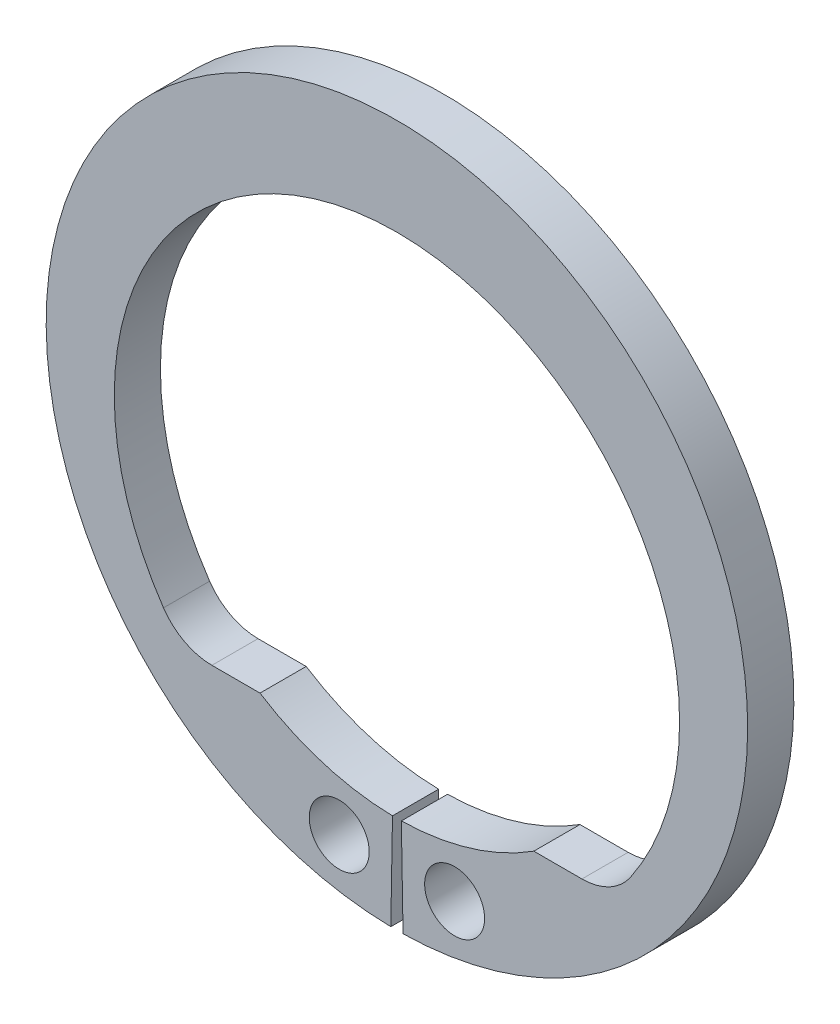
SolidWorks part; units mm, degrees
ref_plane "plane" through (0, 0, 0) normal (0, 0, 1) x (1, 0, 0)
ref_plane "Top" through (0, 0, 0) normal (0, 1, 0) x (1, 0, 0)
ref_plane "Right" through (0, 0, 0) normal (1, 0, 0) x (0, 0, -1)
sketch "Sketch 1" plane through (0, 0, 0) normal (0, 0, 1) x (1, 0, 0)
  line L0 (-5.75, 0) -> (5.75, 0) construction
  line L1 (0, 8.1) -> (0, -8.1) construction
  line L2 (-2.9663, -4.6315) -> (-4.6315, -4.6315) construction
  line L3 (-7.1976, 0) -> (7.1976, 0)
  line L4 (-4.6315, -4.6315) -> (-5.374, -5.374) construction
  line L5 (-4.6315, -4.6315) -> (0, 0) construction
  line L6 (0, 5.5) -> (0, 7.6) construction
  line L7 (0, 7.6) -> (0, 6.55) construction
  line L8 (0, -5.5) -> (0, -50.9099) construction
  line L9 (0, -5.5) -> (0, -6.55) construction
  line L10 (0, 0) -> (-0.1326, -7.5988) construction
  line L11 (0, -6.55) -> (0, -7.6) construction
  line L12 (0, 0) -> (-1.2498, -6.4297) construction
  line L13 (-7.1976, 0) -> (0, -26.6022) construction
  arc A0 (0, 7.6) -> (-4.6315, -4.6315) centre (0, 0.6073) ccw construction
  circle A1 centre (0, 0) radius 7.85 construction
  circle A2 centre (0, 0) radius 7.6 construction
  circle A4 centre (0, 0) radius 5.5 construction
  circle A5 centre (0, 0) radius 8.1 construction
  circle A6 centre (-1.2498, -6.4297) radius 0.65 construction
  arc A7 (-1.2498, -6.4297) -> (-0.1143, -6.549) centre (0, 0) ccw construction
  circle A8 centre (0, 0) radius 6.9478 construction
  point P22 (0, 0)
  point P28 (-7.1976, 0)
  point P32 (0, -26.6022)
  dimension "D1" = 1.4478
  dimension "Cad A" = 16.2
  dimension "D2" = 10
  dimension "Ring ID" = 11
  dimension "Cad C" = 15.7
  dimension "Cad G" = 1.3
  dimension "D4" = 45
  dimension "Cad E" = 2.1
  dimension "Groove Dia" = 11.5
  dimension "D6" = 1
sketch "Sketch2" plane through (0, 0, 0) normal (0, 1, 0) x (0, 0, -1)
  line L0 (-0.5, 0) -> (0.5, 0)
  point P4 (0, 0)
  dimension "Thickness" = 1
sketch "Sketch3" plane through (0, 0, 0) normal (0, 0, 1) x (1, 0, 0)
  line L1 (-2.9663, -4.6315) -> (-4.6315, -4.6315) construction
  line L2 (-2.9663, -4.6315) -> (-4.6315, -4.6315)
  line L3 (0, 0) -> (-0.1326, -7.5988) construction
  line L5 (-0.096, -5.4992) -> (-0.1326, -7.5988)
  line L6 (0, 8.1) -> (0, -8.1) construction
  line L7 (0, 7.6) -> (0, 5.5)
  circle A0 centre (0, -0.6244) radius 6.1244 construction
  circle A2 centre (-1.2498, -6.4297) radius 0.65 construction
  arc A4 (-4.6315, -4.6315) -> (0, 5.5) centre (0, -0.6244) cw
  circle A5 centre (0, 0) radius 5.5 construction
  circle A6 centre (-1.2498, -6.4297) radius 0.65
  arc A8 (-2.9663, -4.6315) -> (-0.096, -5.4992) centre (0, 0) ccw
  circle A9 centre (0, 0) radius 7.6 construction
  arc A10 (0, 7.6) -> (-0.1326, -7.5988) centre (0, 0) ccw
extrude "Boss-Extrude1" add sketch "Sketch3" along normal mid plane 1
fillet "Fillet1" radius 1.27 1 edges at (-4.6315, -4.6315, 0)
mirror "Mirror1" about plane through (0, 0, 0) normal (1, 0, 0) of bodies 109
ref_plane "front" [suppressed] through (0, 0, 0) normal (0.7071, 0.7071, 0) x (0.7071, -0.7071, 0)
ref_axis "Center Axis 1" through (0, 0, -0.8661) along (0, 0, 1)
ref_plane "Contact Plane 1" through (0, 0, 0.5) normal (0, 0, 1) x (1, 0, 0)
ref_plane "Contact Plane 2" through (0, 0, -0.5) normal (0, 0, -1) x (-1, 0, 0)
equation "\"Thickness@Boss-Extrude1\"=\"Thickness@Sketch2\""
